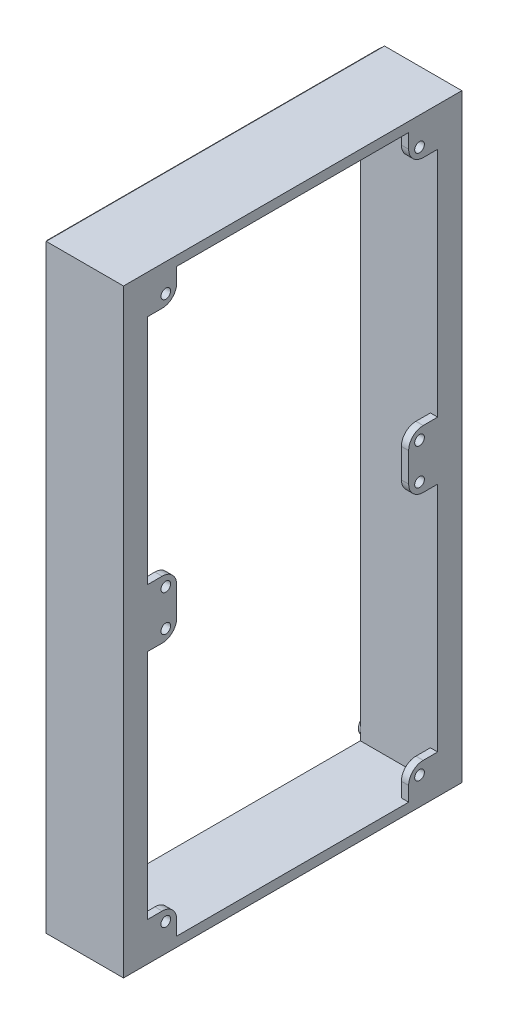
SolidWorks part; units mm, degrees
ref_plane "Front Plane" through (0, 0, 0) normal (1, 0, 0) x (0, 1, 0)
ref_plane "Top Plane" through (0, 0, 0) normal (0, 0, 1) x (0, 1, 0)
ref_plane "Right Plane" through (0, 0, 0) normal (0, 1, 0) x (-1, 0, 0)
sketch "Sketch1" plane through (0, 0, 0) normal (1, 0, 0) x (0, 1, 0)
  line L0 (0, 60) -> (0, -60) construction
  line L1 (-120, -60) -> (120, -60)
  line L2 (-120, -60) -> (-120, 60)
  line L3 (-120, 60) -> (120, 60)
  line L4 (120, -60) -> (120, 60)
  line L5 (-120, -60) -> (120, 60) construction
  line L6 (-120, 60) -> (120, -60) construction
  line L7 (0, 60) -> (0, -60.0055) construction
  line L8 (-120, -60) -> (0, 60) construction
  line L9 (-12, 60) -> (0, 60)
  line L10 (-120, 48) -> (-114, 48)
  line L11 (-120, 48) -> (-120, 60)
  line L12 (-120, 60) -> (-108, 60)
  line L13 (-108, 54) -> (-108, 60)
  line L14 (-12, 60) -> (-12, 54)
  line L15 (-6, 48) -> (0, 48)
  line L16 (0, 60) -> (0, 48)
  line L17 (0, -48) -> (0, -60)
  line L18 (0, -48) -> (-6, -48)
  line L19 (-12, -54) -> (-12, -60)
  line L20 (0, -60) -> (-12, -60)
  line L21 (-108, -60) -> (-120, -60)
  line L22 (-108, -60) -> (-108, -54)
  line L23 (-114, -48) -> (-120, -48)
  line L24 (-120, -60) -> (-120, -48)
  line L25 (0, 48) -> (0, 60)
  line L26 (0, 48) -> (6, 48)
  line L27 (12, 54) -> (12, 60)
  line L28 (0, 60) -> (12, 60)
  line L29 (12, -60) -> (0, -60)
  line L30 (0, -60) -> (0, -48)
  line L31 (6, -48) -> (0, -48)
  line L32 (12, -60) -> (12, -54)
  line L33 (120, -48) -> (120, -60)
  line L34 (120, -60) -> (108, -60)
  line L35 (108, -54) -> (108, -60)
  line L36 (120, -48) -> (114, -48)
  line L37 (108, 60) -> (120, 60)
  line L38 (120, 60) -> (120, 48)
  line L39 (114, 48) -> (120, 48)
  line L40 (108, 60) -> (108, 54)
  line L59 (-124, 70) -> (124, 70)
  line L60 (-124, 70) -> (-124, -70)
  line L61 (-124, -70) -> (124, -70)
  line L62 (124, 70) -> (124, -70)
  line L63 (-124, 70) -> (124, -70) construction
  line L64 (-124, -70) -> (124, 70) construction
  circle A0 centre (-112.5, 52.5) radius 2
  arc A1 (-114, 48) -> (-108, 54) centre (-114, 54) ccw
  arc A2 (-12, 54) -> (-6, 48) centre (-6, 54) ccw
  circle A3 centre (-7.5, 52.5) radius 2
  arc A4 (-6, -48) -> (-12, -54) centre (-6, -54) ccw
  circle A5 centre (-7.5, -52.5) radius 2
  arc A6 (-108, -54) -> (-114, -48) centre (-114, -54) ccw
  circle A7 centre (-112.5, -52.5) radius 2
  arc A8 (6, 48) -> (12, 54) centre (6, 54) ccw
  circle A9 centre (7.5, 52.5) radius 2
  circle A10 centre (7.5, -52.5) radius 2
  arc A11 (12, -54) -> (6, -48) centre (6, -54) ccw
  arc A12 (114, -48) -> (108, -54) centre (114, -54) ccw
  circle A13 centre (112.5, -52.5) radius 2
  arc A14 (108, 54) -> (114, 48) centre (114, 54) ccw
  circle A15 centre (112.5, 52.5) radius 2
  point P0 (0, 0)
  point P12 (0, 0)
  point P16 (-60, 0)
  point P18 (-117, 48)
  point P19 (-108, 57)
  point P22 (-108, 48)
  point P24 (0, 0)
  dimension "D3" = 4
  dimension "D5" = 105
  dimension "D8" = 6
  dimension "D1" = 240
  dimension "D2" = 120
  dimension "D4" = 7.5
  dimension "D6" = 120
  dimension "D7" = 12
  dimension "D9" = 120
  dimension "D10" = 4
  dimension "D11" = 2
  dimension "D12" = 248
  dimension "D13" = 140
extrude "Boss-Extrude2" add sketch "Sketch1" along normal blind 3 contours L10 A1 L13 L3 L2 A0 | L62 L59 L60 L61 L4 L1 L2 L3 | L14 A2 L15 L16 L3 A3 | L26 A8 L27 L3 L16 A9 | L40 A14 L39 L4 L3 A15 | L36 A12 L35 L1 L4 A13 | L32 A11 L31 L17 L1 A10 | L18 A4 L19 L1 L17 A5 | L22 A6 L23 L2 L1 A7 region at (0, -114.4434, -54.4434) region at (0, -5.5566, -54.4434) region at (0, -114.4434, 54.4434) region at (0, 5.5566, -54.4434) region at (0, 114.4434, -54.4434) region at (0, -5.5566, 54.4434) region at (0, 5.5566, 54.4434) region at (0, 114.4434, 54.4434) region at (0, 0, 67.1521)
extrude "Boss-Extrude5" add sketch "Sketch1<6>" against normal blind 29 contours L62 L59 L60 L61 L4 L1 L2 L3 region at (0, 0, 67.1521)
sketch "Sketch1<6>" plane through (0, 0, 0) normal (1, 0, 0) x (0, 1, 0) same geometry as "Sketch1"
sketch "Sketch14" plane through (-29, 0, 0) normal (-1, 0, 0) x (0, -1, 0)
  line L0 (-124, 70) -> (-120, 60) construction
  line L1 (0, 0) -> (-50000, 0) construction
  line L2 (-124, 70) -> (-124, -70) construction
  line L3 (0, 0) -> (0, -50000) construction
  line L4 (120, -60) -> (-120, -60) construction
  line L5 (124, 70) -> (-124, 70) construction
  line L6 (-123.6, 69) -> (123, 69)
  line L7 (-123.6, 69) -> (-123.6, -69)
  line L8 (-123.6, -69) -> (123, -69)
  line L9 (123, 69) -> (123, -69)
  line L10 (-123.2, 68.6) -> (122.6, 68.6)
  line L11 (122.6, 68.6) -> (122.6, -68.6)
  line L12 (-123.2, -68.6) -> (122.6, -68.6)
  line L13 (-123.2, 68.6) -> (-123.2, -68.6)
  line L14 (124, 70) -> (124, -70) construction
  line L15 (124, -70) -> (-124, -70) construction
  line L17 (120, 60) -> (-120, 60) construction
  circle A0 centre (-116.0377, 63.95) radius 3.15
  circle A1 centre (-116.0377, 63.95) radius 3.95
  circle A2 centre (116.0377, 63.95) radius 3.15
  circle A3 centre (116.0377, 63.95) radius 3.95
  circle A4 centre (116.0377, -63.95) radius 3.15
  circle A5 centre (116.0377, -63.95) radius 3.95
  circle A6 centre (-116.0377, -63.95) radius 3.95
  circle A7 centre (-116.0377, -63.95) radius 3.15
  point P6 (-120, 60)
  point P13 (-124, 0)
  point P18 (0, -60)
  point P44 (-180, 60)
  point P45 (-120, 60)
  point P47 (0, 0)
  point P48 (-120, 60)
  point P49 (0, 0)
  point P50 (0, 0)
  point P51 (-114.2523, 61.3231)
  point P52 (-120, 60)
  point P54 (-114.6335, 66.4975)
  dimension "D1" = 6.3
  dimension "D8" = 3.95
  dimension "D3" = 1
  dimension "D4" = 0.4
  dimension "D5" = 1
  dimension "D6" = 1
  dimension "D7" = 10
  dimension "D2" = 0.8
extrude "Boss-Extrude7" add sketch "Sketch14" along normal blind 0.2 contours L7 L8 L9 L6 | L13 L12 L11 L10
extrude "Boss-Extrude9" add sketch "Sketch14<4>" along normal blind 0.8 contours A1 | A3 | A5 | A6
sketch "Sketch14<4>" plane through (-29, 0, 0) normal (-1, 0, 0) x (0, -1, 0) same geometry as "Sketch14"
extrude "Mounting magnet holes" cut sketch "Sketch14<5>" along normal blind 0.6 and the other way blind 1.5 contours A0 | A7 | A4 | A2
sketch "Sketch14<5>" plane through (-29, 0, 0) normal (-1, 0, 0) x (0, -1, 0) same geometry as "Sketch14"
sketch "Sketch17" plane through (-29.2, 0, 0) normal (-1, 0, 0) x (0, -1, 0)
  line L10 (-123.2, 68.6) -> (122.6, 68.6)
  line L11 (-123.2, 68.6) -> (-123.2, -68.6)
  line L12 (123.2, 69.2) -> (-123.8, 69.2)
  line L13 (-123.8, 69.2) -> (-123.8, -69.2)
  line L14 (-123.8, -69.2) -> (123.2, -69.2)
  line L15 (123.2, -69.2) -> (123.2, 69.2)
  line L16 (123.2, 69.2) -> (-123.8, 69.2)
  line L17 (-123.8, 69.2) -> (-123.8, -69.2)
  line L18 (-123.8, -69.2) -> (123.2, -69.2)
  line L19 (123.2, -69.2) -> (123.2, 69.2)
  line L20 (-123.2, -68.6) -> (122.6, -68.6)
  line L21 (122.6, 68.6) -> (122.6, -68.6)
  dimension "D1" = 0.2
extrude "Boss-Extrude10" add sketch "Sketch17" along normal blind 0.4
chamfer "Chamfer1" distance 0.4 angle 30 4 edges at (-29.6, 0.3, -69.2) (-29.6, -123.2, 0) (-29.6, 123.8, 0) (-29.6, 0.3, 69.2) first distance on face at (-29.4, 0.3, -69.2) first distance on face at (-29.4, -123.2, 0) first distance on face at (-29.4, 123.8, 0) first distance on face at (-29.4, 0.3, 69.2)
sketch "Sketch18" plane through (3, 0, 0) normal (1, 0, 0) x (0, 1, 0)
  line L0 (-124, 70) -> (124, 70) construction
  line L1 (-124, 70) -> (-124, -70) construction
  line L2 (0, 0) -> (-358.4227, 0) construction
  line L3 (0, 0) -> (0, 85.8788) construction
  circle A0 centre (-119, 65) radius 3.15
  circle A2 centre (119, 65) radius 3.15
  circle A4 centre (119, -65) radius 3.15
  circle A7 centre (-119, -65) radius 3.15
  dimension "D1" = 6.3
  dimension "D2" = 5
  dimension "D3" = 5
  dimension "D4" = 6.3
extrude "Cover magnet holes" cut sketch "Sketch18" against normal blind 2.1 from offset 0.4 offset against normal yes
